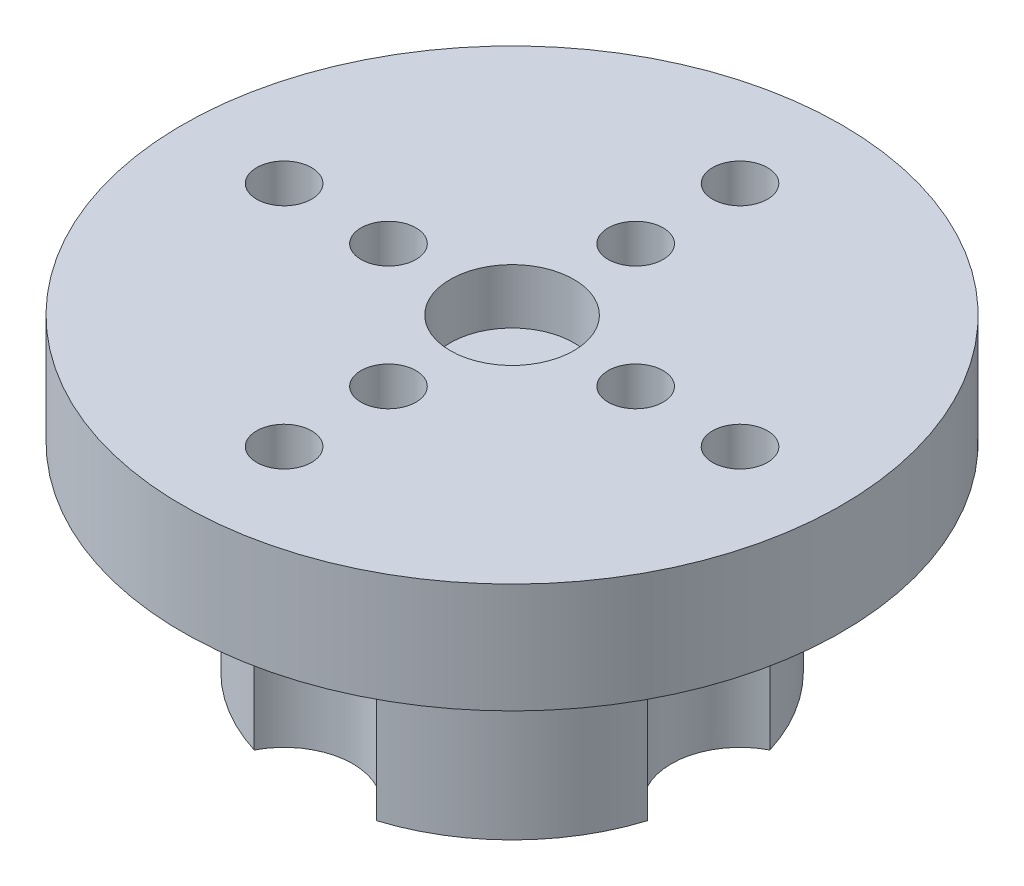
SolidWorks part; units mm, degrees
material "ABS PC"
ref_plane "Front Plane" through (0, 0, 0) normal (0, 0, 1) x (1, 0, 0)
ref_plane "Top Plane" through (0, 0, 0) normal (0, 1, 0) x (1, 0, 0)
ref_plane "Right Plane" through (0, 0, 0) normal (1, 0, 0) x (0, 0, -1)
sketch "Sketch1" plane through (0, 0, 0) normal (0, 0, 1) x (1, 0, 0)
  line L0 (0, 0) -> (0, 15.6368) construction
  line L1 (0, 11.25) -> (0, 0)
  line L2 (0, 11.25) -> (12, 11.25)
  line L3 (8.5, 5.25) -> (8.5, 7.25)
  line L4 (8.5, 5.25) -> (7.5, 5.25)
  line L5 (7.5, 5.25) -> (7.5, 0)
  line L7 (8.5, 7.25) -> (12, 7.25)
  line L8 (12, 7.25) -> (12, 11.25)
  line L10 (0, 0) -> (7.5, 0)
  dimension "D1" = 7.5
  dimension "D2" = 1
  dimension "D3" = 5.25
  dimension "D4" = 2
  dimension "D5" = 12
  dimension "D6" = 4
revolve "Revolve1" add sketch "Sketch1" angle 360 about L0
sketch "Sketch2" plane through (0, 11.25, 0) normal (0, 1, 0) x (1, 0, 0)
  circle A0 centre (8.3, 0) radius 1
  circle A1 centre (4.5, 0) radius 1
  dimension "D2" = 2
  dimension "D3" = 2
  dimension "D4" = 4.5
  dimension "D1" = 8.3
extrude "Cut-Extrude1" cut sketch "Sketch2" against normal through all
pattern_circular "CirPattern1" count 4 over 360 about axis through (0, 11.25, 0) along (0, -1, 0) of "Cut-Extrude1"
sketch "Sketch3" plane through (0, 0, 0) normal (0, -1, 0) x (1, 0, 0)
  circle A0 centre (0, 8.3) radius 2.5
  circle A1 centre (8.3, 0) radius 2.5
  circle A2 centre (0, -8.3) radius 2.5
  circle A3 centre (-8.3, 0) radius 2.5
  point P12 (0, 0)
  dimension "D1" = 5
  dimension "D2" = 4
extrude "Cut-Extrude2" cut sketch "Sketch3" against normal blind 8
sketch "Sketch4" plane through (0, 11.25, 0) normal (0, 1, 0) x (1, 0, 0)
  circle A0 centre (0, 0) radius 2.25
  dimension "D1" = 4.5
extrude "Cut-Extrude3" cut sketch "Sketch4" against normal blind 2
